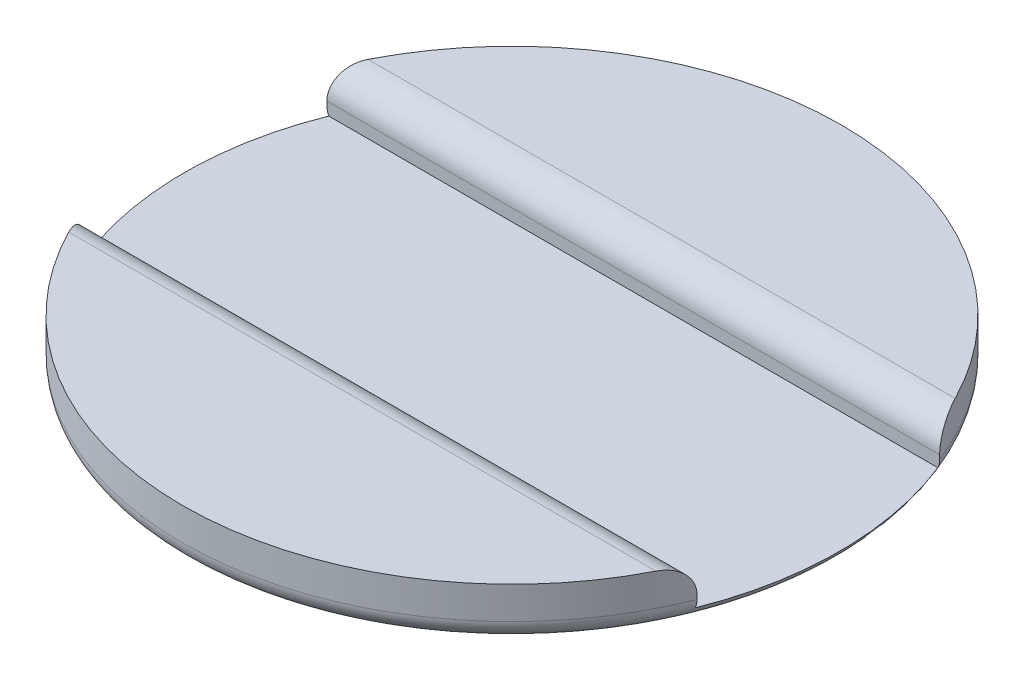
SolidWorks part; units mm, degrees
ref_plane "Front Plane" through (0, 0, 0) normal (0, 0, 1) x (1, 0, 0)
ref_plane "Top Plane" through (0, 0, 0) normal (0, 1, 0) x (1, 0, 0)
ref_plane "Right Plane" through (0, 0, 0) normal (1, 0, 0) x (0, 0, -1)
sketch "Sketch1" plane through (0, 0, 0) normal (0, 1, 0) x (1, 0, 0)
  line L0 (-7.5778, 3) -> (7.5778, 3)
  line L1 (-7.5778, -3) -> (7.5778, -3)
  circle A0 centre (0, 0) radius 8.15
  point P9 (-0.0853, -2.9235)
  dimension "D1" = 16.3
  dimension "D2" = 3
  dimension "D3" = 3
extrude "Boss-Extrude1" add sketch "Sketch1" along normal blind 1.3 contours L0 A0 | L1 A0 region at (0, 0, -5.1285) region at (0, 0, 5.1285)
extrude "Boss-Extrude3" add sketch "Sketch1<4>" along normal blind 0.3 contours L1 A0 L0 region at (0, 0, 0)
sketch "Sketch1<4>" plane through (0, 0, 0) normal (0, 1, 0) x (1, 0, 0) same geometry as "Sketch1"
fillet "Fillet3" radius 0.7 2 edges at (0, 1.3, 3) (0, 1.3, -3)
fillet "Fillet4" radius 0.5 1 edges at (0, 0, 8.15)
